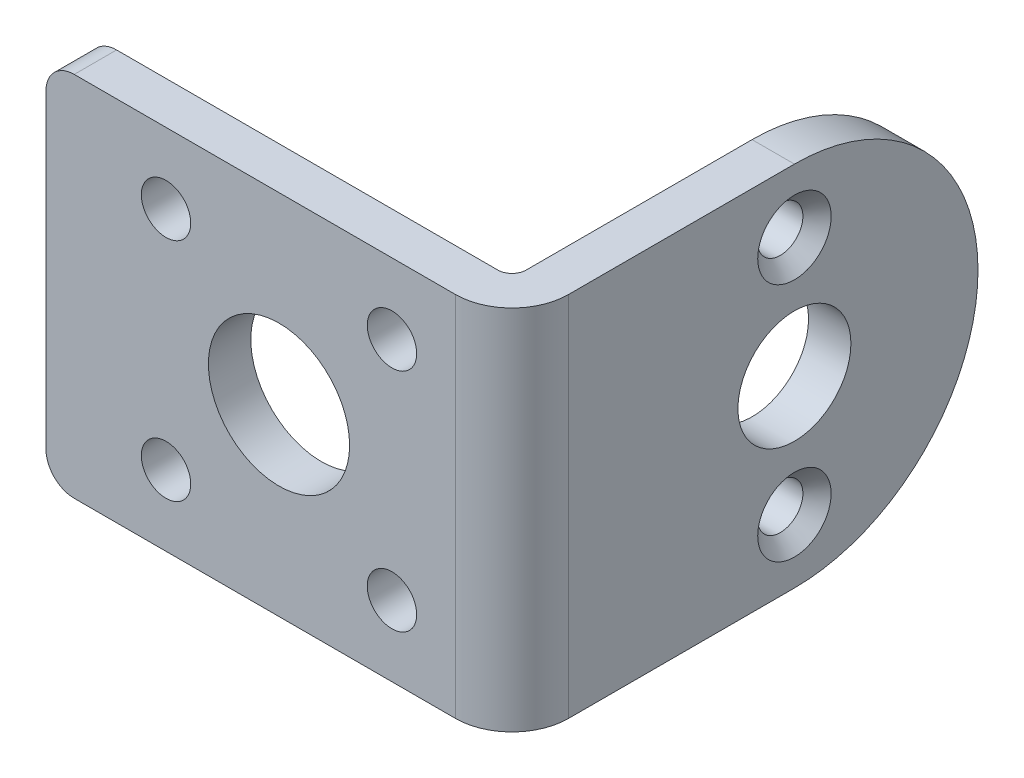
SolidWorks part; units mm, degrees
ref_plane "Front Plane" through (0, 0, 0) normal (0, 0, 1) x (1, 0, 0)
ref_plane "Top Plane" through (0, 0, 0) normal (0, 1, 0) x (1, 0, 0)
ref_plane "Right Plane" through (0, 0, 0) normal (1, 0, 0) x (0, 0, -1)
sketch "Sketch1" plane through (0, 0, 0) normal (0, 1, 0) x (1, 0, 0)
  line L0 (0, 0) -> (0, 33)
  line L1 (0, 0) -> (-33, 0)
  line L2 (-3, 3) -> (-3, 33)
  line L3 (-3, 3) -> (-33, 3)
  line L4 (-33, 3) -> (-33, 0)
  line L5 (-3, 33) -> (0, 33)
  dimension "D1" = 33
  dimension "D2" = 33
  dimension "D3" = 3
extrude "Boss-Extrude1" add sketch "Sketch1" along normal blind 26
sketch "Sketch2" plane through (0, 0, 0) normal (0, 0, 1) x (1, 0, 0)
  line L0 (-16.5, 26) -> (-16.5, 0) construction
  line L1 (-33, 26) -> (0, 26) construction
  line L2 (-33, 0) -> (0, 0) construction
  line L4 (-24.5, 5) -> (-8.5, 5) construction
  line L5 (-24.5, 5) -> (-24.5, 21) construction
  line L6 (-24.5, 21) -> (-8.5, 21) construction
  line L7 (-8.5, 5) -> (-8.5, 21) construction
  line L8 (-24.5, 5) -> (-8.5, 21) construction
  line L9 (-24.5, 21) -> (-8.5, 5) construction
  circle A0 centre (-16.5, 13) radius 5
  circle A1 centre (-24.5, 21) radius 1.75
  circle A2 centre (-8.5, 21) radius 1.75
  circle A3 centre (-8.5, 5) radius 1.75
  circle A4 centre (-24.5, 5) radius 1.75
  dimension "D1" = 10
  dimension "D4" = 3.5
  dimension "D2" = 16
  dimension "D3" = 16
  dimension "D5" = 2
  dimension "D6" = 2
extrude "Cut-Extrude1" cut sketch "Sketch2" against normal blind 26 contours A0 | A4 | A3 | A2 | A1
fillet "Fillet1" radius 13 2 edges at (-1.5, 0, -33) (-1.5, 26, -33)
sketch "Sketch4" plane through (0, 0, 0) normal (1, 0, 0) x (0, 0, -1)
  line L0 (20, 26) -> (20, 0) construction
  line L1 (20, 21.5) -> (20, 4.5) construction
  circle A0 centre (20, 13) radius 4
  circle A1 centre (20, 21.5) radius 1.6
  circle A2 centre (20, 4.5) radius 1.6
  point P10 (20, 13)
  dimension "D1" = 8
  dimension "D3" = 3.2
  dimension "D4" = 3.2
  dimension "D2" = 17
extrude "Cut-Extrude2" cut sketch "Sketch4" against normal blind 26
fillet "Fillet2" radius 1 1 edges at (-3, 13, -3)
fillet "Fillet3" radius 4 1 edges at (0, 13, 0)
fillet "Fillet4" radius 2 2 edges at (-33, 0, -1.5) (-33, 26, -1.5)
chamfer "Chamfer1" distance 1 angle 45 2 edges at (0, 4.5, -21.6) (0, 21.5, -21.6)
